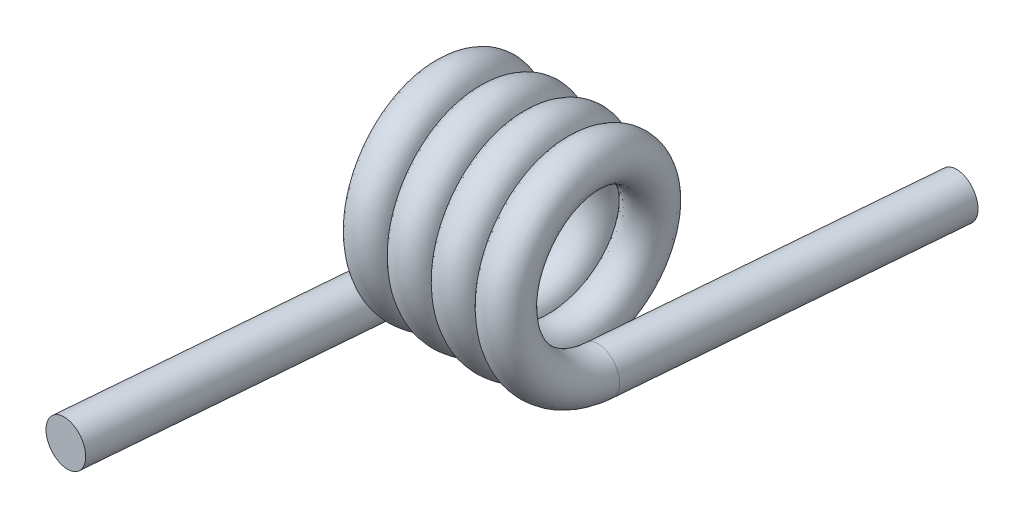
SolidWorks part; units mm, degrees
note: '?' marks a value the reader was unsure of.
material "AISI 304"
ref_plane "Front" through (0, 0, 0) normal (0, 0, 1) x (1, 0, 0)
ref_plane "Top" through (0, 0, 0) normal (0, 1, 0) x (1, 0, 0)
ref_plane "Right" through (0, 0, 0) normal (1, 0, 0) x (0, 0, -1)
sketch "Sketch1" plane through (0, 0, 0) normal (1, 0, 0) x (0, 0, -1)
  line L0 (0, 0) -> (0, -1.4) construction
  line L1 (0, -1.4) -> (0, -1.9) construction
  line L2 (0, -1.9) -> (0, -2.4) construction
  circle A0 centre (0, 0) radius 1.4 construction
  circle A1 centre (0, 0) radius 2.4 construction
  circle A2 centre (0, 0) radius 1.9
  circle A3 centre (0, -1.9) radius 0.5 construction
  circle A4 centre (0, 0) radius 1.325 construction
  dimension "D1" = 0.075
  dimension "Wire Dia" = 1
  dimension "D2" = 2.8
  dimension "Spring OD" = 4.8
  dimension "Max Rod OD" = 2.65
curve "Helix/Spiral1" pitch 1.01 height 4.04 turns 4
ref_plane "Plane1" through (0, -1.9, 0) normal (0.0843, 0, -0.9964) x (0.9925, 0.0893, 0.084)
sketch "Sketch2" plane through (0, -1.9, 0) normal (0.0843, 0, -0.9964) x (0.9925, 0.0893, 0.084)
  circle A0 centre (0, 0) radius 0.5
  dimension "D1" = 1
sweep "Sweep1" add profiles "Sketch2" path "Helix/Spiral1"
sketch "Sketch3" plane through (0, 0, 0) normal (-0.0843, 0, 0.9964) x (-0.9925, -0.0893, -0.084)
  circle A1 centre (0.1696, 1.8924) radius 0.5
  circle A2 centre (0.1696, 1.8924) radius 0.5
  dimension "D1" = 0
extrude "Extrude1" add sketch "Sketch3" along normal blind 7.62
sketch "Sketch4" plane through (0.0287, 0, -0.3394) normal (0.0843, 0, -0.9964) x (0.9636, -0.2548, 0.0815)
  circle A1 centre (4.3768, 0.8118) radius 0.5
  circle A2 centre (4.3768, 0.8118) radius 0.5
  dimension "D1" = 0
extrude "Extrude2" add sketch "Sketch4" along normal blind 7.62
sketch "Sketch5" plane through (0, 0, 0) normal (1, 0, 0) x (0, 0, -1)
  circle A0 centre (0, 0) radius 1.325 construction
  circle A1 centre (0, 0) radius 1.325
ref_axis "Axis1" through (-0.6472, 0, 0) along (1, 0, 0)?
equation "\"D4@Helix/Spiral1\" = \"Wire Dia@Sketch1\" + .01"
equation "\"D1@Sketch2\"=\"Wire Dia@Sketch1\""
equation "\"D1@Extrude2\"=\"Leg Length@Extrude1\""
